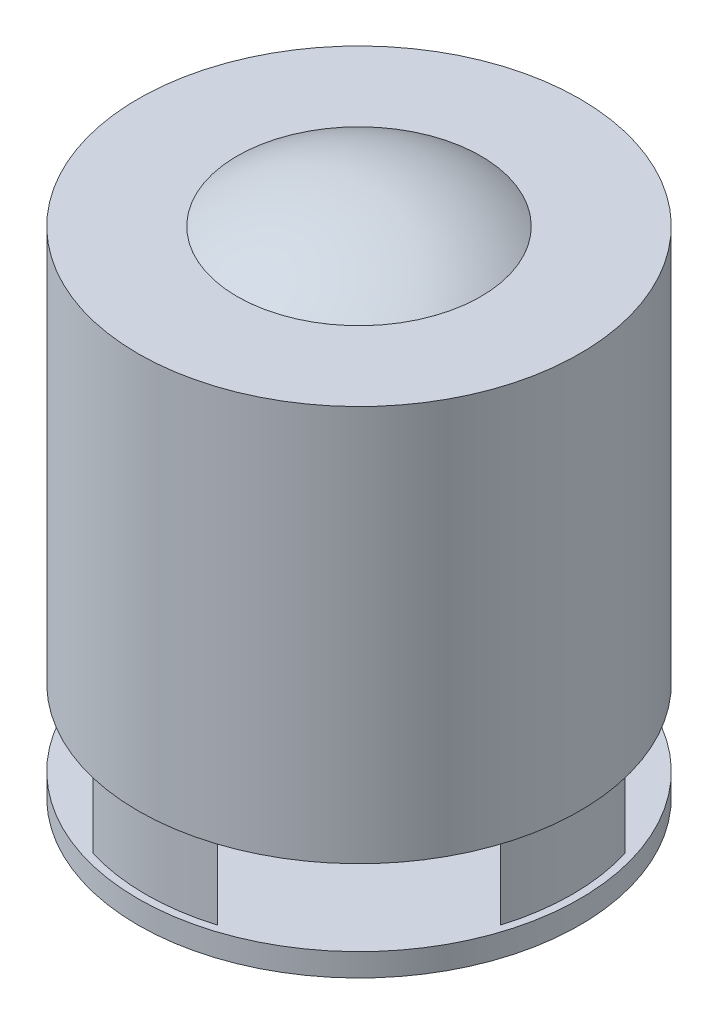
SolidWorks part; units mm, degrees
ref_plane "Alzado" through (0, 0, 0) normal (0, 0, 1) x (1, 0, 0)
ref_plane "Planta" through (0, 0, 0) normal (0, 1, 0) x (1, 0, 0)
ref_plane "Vista lateral" through (0, 0, 0) normal (1, 0, 0) x (0, 0, -1)
sketch "Croquis1" plane through (0, 0, 0) normal (0, 1, 0) x (1, 0, 0)
  circle A0 centre (0, 0) radius 29
  dimension "D1" = 58
extrude "Saliente-Extruir1" add sketch "Croquis1" along normal blind 52
sketch "Croquis2" plane through (0, 0, 0) normal (0, -1, 0) x (1, 0, 0)
  line L0 (0, -28.0015) -> (0, -25.4355) construction
  line L1 (25.4355, 6) -> (25.4355, -6)
  line L2 (-6, 25.4355) -> (6, 25.4355)
  line L3 (-6, 25.4355) -> (-8.1868, 26.778)
  line L4 (6, 25.4355) -> (8.1868, 26.778)
  line L5 (0, 25.4355) -> (0, 28.0015) construction
  line L6 (25.4355, 6) -> (26.778, 8.1868)
  line L7 (25.4355, -6) -> (26.778, -8.1868)
  line L8 (6, -25.4355) -> (-6, -25.4355)
  line L9 (6, -25.4355) -> (8.1868, -26.778)
  line L10 (-6, -25.4355) -> (-8.1868, -26.778)
  line L11 (-25.4355, -6) -> (-25.4355, 6)
  line L12 (-25.4355, -6) -> (-26.778, -8.1868)
  line L13 (-25.4355, 6) -> (-26.778, 8.1868)
  arc A2 (8.1868, 26.778) -> (-8.1868, 26.778) centre (0, 0) ccw
  arc A3 (26.778, -8.1868) -> (26.778, 8.1868) centre (0, 0) ccw
  arc A4 (-8.1868, -26.778) -> (8.1868, -26.778) centre (0, 0) ccw
  arc A5 (-26.778, 8.1868) -> (-26.778, -8.1868) centre (0, 0) ccw
  point P7 (0, 0)
  point P12 (0, 25.4355)
  point P13 (0, 25.4355)
  point P28 (0, 0)
  dimension "D1" = 4
  dimension "D3" = 12
  dimension "D4" = 2.566
extrude "Saliente-Extruir2" add sketch "Croquis2" along normal blind 10
sketch "Croquis3" plane through (0, -10, 0) normal (0, -1, 0) x (1, 0, 0)
  circle A0 centre (0, 0) radius 29
  dimension "D1" = 58
extrude "Saliente-Extruir3" add sketch "Croquis3" along normal blind 3
sketch "Croquis6" plane through (0, 52, 0) normal (0, 1, 0) x (1, 0, 0)
  circle A0 centre (0, 0) radius 16
  dimension "D1" = 32
extrude "Saliente-Extruir4" add sketch "Croquis6" along normal blind 0.001
dome "Cúpula1" faces to dome 1 distance 5 reverse direction no elliptical dome no face at (0, 52.001, 16) parameters "D1"=5
sketch "Croquis7" plane through (0, -13, 0) normal (0, -1, 0) x (1, 0, 0)
  line L0 (0, 0) -> (0, 12) construction
  circle A0 centre (0, 12) radius 2.05
  circle A1 centre (10.3923, -6) radius 2.05
  circle A2 centre (-10.3923, -6) radius 2.05
  point P11 (0, 0)
  dimension "D2" = 4.1
  dimension "D1" = 12
  dimension "D3" = 3
extrude "Cortar-Extruir1" cut sketch "Croquis7" against normal blind 3
